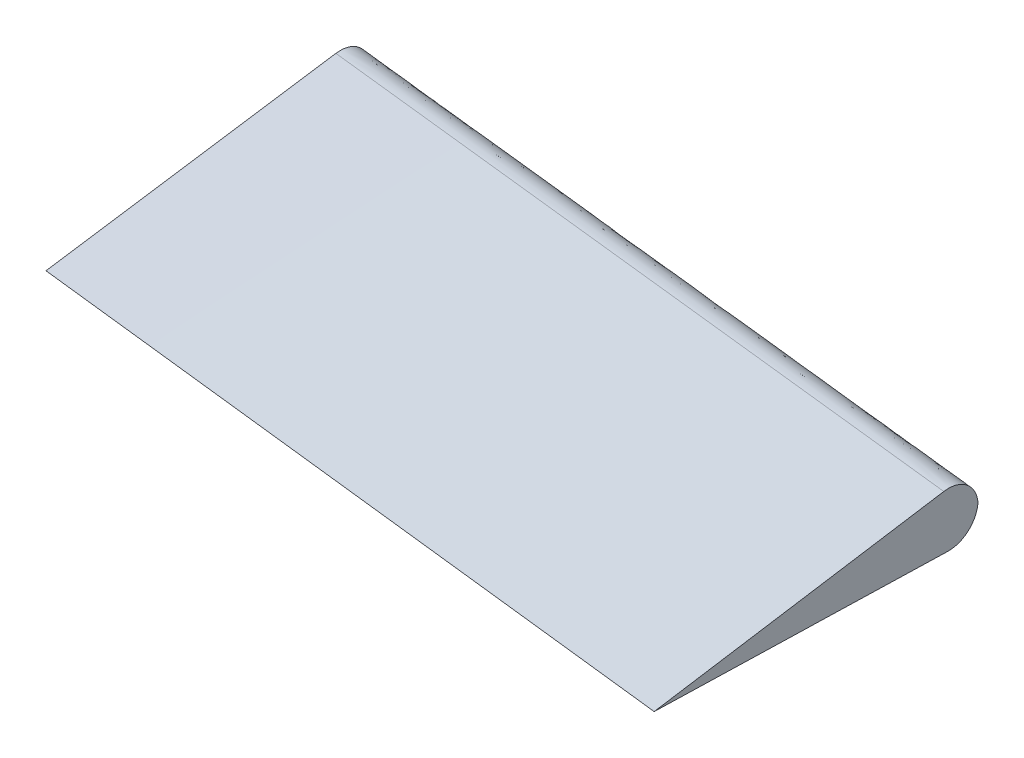
SolidWorks part; units mm, degrees
material "PET"
ref_plane "Alzado" through (0, 0, 0) normal (0, 0, 1) x (1, 0, 0)
ref_plane "Planta" through (0, 0, 0) normal (0, 1, 0) x (1, 0, 0)
ref_plane "Vista lateral" through (0, 0, 0) normal (1, 0, 0) x (0, 0, -1)
sketch "Croquis1" plane through (0, 0, 0) normal (1, 0, 0) x (0, 0, -1)
  line L0 (27.5001, 5.1042) -> (27.5001, -5.1042)
  line L1 (27.5001, -5.1042) -> (-27.5001, -3.1123)
  line L2 (-27.5001, -3.1123) -> (27.5001, 5.1042)
ref_plane "Plano1" through (115.97, 0, 0) normal (1, 0, 0) x (0, 0, -1)
sketch "Croquis2" plane through (115.97, 0, 0) normal (1, 0, 0) x (0, 0, -1)
  line L0 (14.7901, 5.1042) -> (14.7901, -5.1042)
  line L1 (14.7901, -5.1042) -> (-40.2101, -3.5928)
  line L2 (-40.2101, -3.5928) -> (14.7901, 5.1042)
  line L4 (27.5001, 5.1042) -> (5.9268, 5.1042) construction
  dimension "D1" = 12.71
  dimension "D2" = 10.2085
loft "Recubrir1" add profiles "Croquis1", "Croquis2" connector at (0, 5.1042, -27.5001) connector at (115.97, 5.1042, -14.7901)
fillet "Redondeo1" radius 5 2 edges
